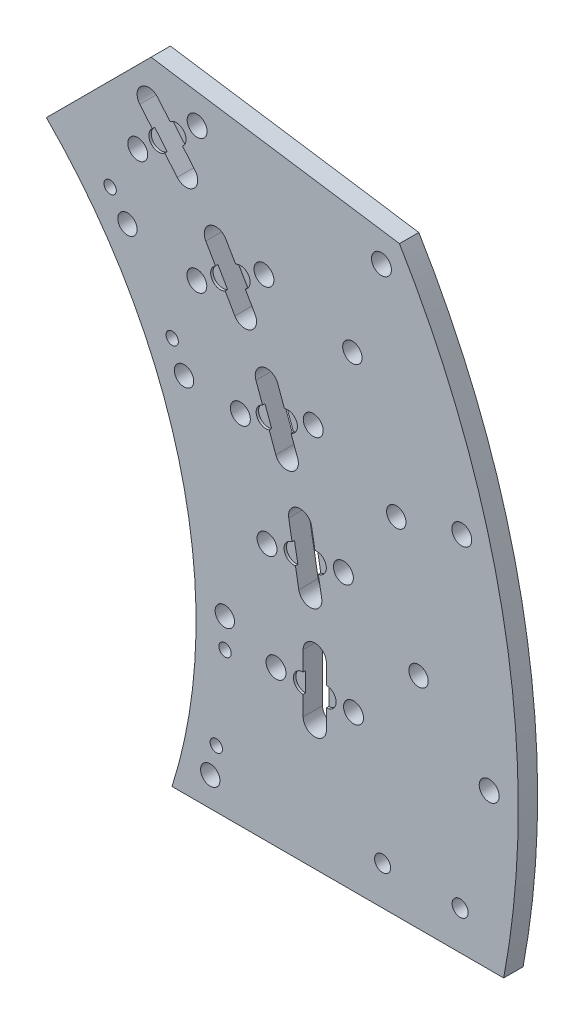
SolidWorks part; units mm, degrees
material "6061-T6 (SS)"
ref_plane "Front Plane" through (0, 0, 0) normal (0, 0, 1) x (1, 0, 0)
ref_plane "Top Plane" through (0, 0, 0) normal (0, 1, 0) x (1, 0, 0)
ref_plane "Right Plane" through (0, 0, 0) normal (1, 0, 0) x (0, 0, -1)
sketch "Sketch1" plane through (0, 0, 0) normal (0, 0, 1) x (1, 0, 0)
  line L0 (0, 0) -> (177.8, 0) construction
  line L1 (176.8984, 6.1774) -> (0, 0) construction
  line L2 (0, 0) -> (121.7947, 121.7947) construction
  line L3 (121.7947, 121.7947) -> (122.9173, 122.9173) construction
  line L4 (144.995, 101.5266) -> (0, 0) construction
  line L5 (0, 0) -> (163.5325, 67.7374) construction
  line L6 (167.4812, 0) -> (167.4812, -50.8) construction
  line L8 (159.5911, -50.8) -> (167.4812, -50.8) construction
  line L9 (172.1267, -41.275) -> (0, 0) construction
  line L10 (159.5911, -50.8) -> (268.2828, -50.8)
  line L11 (118.4271, 118.4271) -> (152.7152, 152.7152)
  line L12 (177.8, 0) -> (193.675, 0) construction
  line L13 (202.565, 0) -> (210.185, 0) construction
  line L14 (210.185, 0) -> (219.075, 0) construction
  line L15 (193.675, 0) -> (202.565, 0) construction
  line L16 (202.565, 0) -> (202.565, 9.525)
  line L17 (202.565, 0) -> (202.565, -9.525)
  line L18 (210.185, 9.525) -> (210.185, 0)
  line L19 (210.185, 0) -> (210.185, -9.525)
  line L20 (202.565, -9.525) -> (210.185, -9.525) construction
  line L21 (202.565, 9.525) -> (210.185, 9.525) construction
  line L22 (210.185, 9.525) -> (219.075, 0) construction
  line L23 (202.565, 9.525) -> (193.675, 0) construction
  line L24 (199.4876, 35.175) -> (201.1416, 25.7947)
  line L25 (199.4876, 35.175) -> (197.8336, 44.5553)
  line L26 (205.3378, 45.8785) -> (206.9918, 36.4982)
  line L27 (206.9918, 36.4982) -> (208.6458, 27.1179)
  line L28 (190.3488, 69.2813) -> (193.6066, 60.3307)
  line L29 (190.3488, 69.2813) -> (187.0911, 78.2319)
  line L30 (194.2516, 80.8381) -> (197.5093, 71.8875)
  line L31 (197.5093, 71.8875) -> (200.767, 62.9369)
  line L32 (175.4264, 101.2825) -> (180.1889, 93.0336)
  line L33 (175.4264, 101.2825) -> (170.6639, 109.5314)
  line L34 (177.263, 113.3414) -> (182.0255, 105.0925)
  line L35 (182.0255, 105.0925) -> (186.788, 96.8436)
  line L36 (155.1738, 130.2063) -> (161.2963, 122.9097)
  line L37 (155.1738, 130.2063) -> (149.0512, 137.5028)
  line L38 (154.8885, 142.4009) -> (161.0111, 135.1043)
  line L39 (161.0111, 135.1043) -> (167.1336, 127.8077)
  line L40 (0, 0) -> (193.675, 0) construction
  line L41 (0, 0) -> (190.7326, 33.6313) construction
  line L42 (0, 0) -> (254, 0) construction
  line L43 (254, 0) -> (263.525, 0) construction
  line L44 (254.5456, 68.2053) -> (0, 0) construction
  line L45 (152.7152, 152.7152) -> (234.123, 140.5088)
  line L46 (167.8212, 140.8187) -> (228.2193, 131.7625) construction
  line L47 (254.5456, 68.2053) -> (263.746, 70.6705) construction
  line L48 (0, 0) -> (240.3818, 21.0307) construction
  line L49 (0, 0) -> (240.3818, 21.0307) construction
  line L50 (0, 0) -> (233.0779, 62.453) construction
  line L51 (215.9, -50.8) -> (215.9, -25.4) construction
  line L52 (215.9, -25.4) -> (266.7, -25.4) construction
  line L53 (266.7, -25.4) -> (266.7, -50.8) construction
  line L54 (228.6, -38.1) -> (254, -38.1) construction
  line L55 (0, 0) -> (159.6519, 76.4361) construction
  line L56 (0, 0) -> (139.3238, 109.1792) construction
  arc A0 (172.2437, 0) -> (121.7947, 121.7947) centre (0, 0) ccw construction
  arc A1 (173.8312, 0) -> (122.9173, 122.9173) centre (0, 0) ccw construction
  circle A2 centre (176.8984, 6.1774) radius 3.175
  circle A3 centre (144.995, 101.5266) radius 3.175
  circle A4 centre (163.5325, 67.7374) radius 3.175
  arc A5 (167.4812, 0) -> (118.4271, 118.4271) centre (0, 0) ccw
  arc A6 (167.4812, 0) -> (159.5911, -50.8) centre (0, 0) cw
  arc A7 (173.8312, 0) -> (166.2428, -50.8) centre (0, 0) cw construction
  circle A8 centre (172.1267, -41.275) radius 3.175
  circle A9 centre (193.675, 0) radius 9.525 construction
  circle A10 centre (219.075, 0) radius 9.525 construction
  arc A11 (202.565, -9.525) -> (210.185, -9.525) centre (206.375, -9.525) ccw
  arc A12 (202.565, 9.525) -> (210.185, 9.525) centre (206.375, 9.525) cw
  circle A13 centre (193.675, 0) radius 3.2639
  circle A14 centre (219.075, 0) radius 3.2639
  circle A15 centre (215.7468, 38.042) radius 3.2639
  arc A16 (201.1416, 25.7947) -> (208.6458, 27.1179) centre (204.8937, 26.4563) ccw
  arc A17 (197.8336, 44.5553) -> (205.3378, 45.8785) centre (201.5857, 45.2169) cw
  circle A18 centre (190.7326, 33.6313) radius 3.2639
  circle A19 centre (205.8632, 74.9281) radius 3.2639
  arc A20 (193.6066, 60.3307) -> (200.767, 62.9369) centre (197.1868, 61.6338) ccw
  arc A21 (187.0911, 78.2319) -> (194.2516, 80.8381) centre (190.6713, 79.535) cw
  circle A22 centre (181.995, 66.2408) radius 3.2639
  circle A23 centre (189.7245, 109.5375) radius 3.2639
  arc A24 (180.1889, 93.0336) -> (186.788, 96.8436) centre (183.4885, 94.9386) ccw
  arc A25 (170.6639, 109.5314) -> (177.263, 113.3414) centre (173.9635, 111.4364) cw
  circle A26 centre (167.7275, 96.8375) radius 3.2639
  circle A27 centre (167.8212, 140.8187) radius 3.2639
  arc A28 (161.2963, 122.9097) -> (167.1336, 127.8077) centre (164.215, 125.3587) ccw
  arc A29 (149.0512, 137.5028) -> (154.8885, 142.4009) centre (151.9699, 139.9519) cw
  circle A30 centre (148.3637, 124.4919) radius 3.2639
  circle A31 centre (263.525, 0) radius 3.2639
  circle A32 centre (254.5456, 68.2053) radius 3.2639
  circle A33 centre (228.2193, 131.7625) radius 3.2639
  arc A34 (234.123, 140.5088) -> (268.2828, -50.8) centre (0, 0) cw
  circle A36 centre (240.3818, 21.0307) radius 3.175
  circle A37 centre (233.0779, 62.453) radius 3.175
  circle A38 centre (218.6921, 101.9778) radius 3.175
  arc A39 (210.185, 0) -> (203.9537, -50.8) centre (0, 0) cw construction
  circle A40 centre (228.6, -38.1) radius 2.6289
  circle A41 centre (254, -38.1) radius 2.6289
  circle A42 centre (159.6519, 76.4361) radius 9.525 construction
  circle A43 centre (159.6519, 76.4361) radius 2.0193
  circle A44 centre (159.6519, 76.4361) radius 3.175 construction
  circle A45 centre (139.3238, 109.1792) radius 2.0193
  circle A46 centre (139.3238, 109.1792) radius 9.525 construction
  circle A47 centre (176.9746, -3.3473) radius 2.0193
  circle A48 centre (176.9746, -3.3473) radius 9.525 construction
  circle A49 centre (174.0977, -31.9562) radius 2.0193
  circle A50 centre (174.0977, -31.9562) radius 9.525 construction
  point P3 (172.2437, 0)
  point P96 (0, 0)
  point P114 (266.7, -38.1)
  point P121 (177.8, -4.2997)
  point P124 (173.8312, -31.5473)
  point P132 (0, 0)
  dimension "D3" = 1.5875
  dimension "D4" = 6.35
  dimension "D5" = 2
  dimension "D7" = 10
  dimension "D8" = 6.35
  dimension "D9" = 6.35
  dimension "D11" = 6.35
  dimension "D13" = 6.35
  dimension "D15" = 19.05
  dimension "D16" = 7.62
  dimension "D17" = 19.05
  dimension "D21" = 15.875
  dimension "D22" = 6.5278
  dimension "D23" = 6.5278
  dimension "D28" = 6.5278
  dimension "D32" = 9.525
  dimension "D33" = 5
  dimension "D34" = 241.3
  dimension "D35" = 6.35
  dimension "D38" = 25.4
  dimension "D40" = 5.2578
  dimension "D41" = 5.2578
  dimension "D43" = 12.7
  dimension "D45" = 263.525
  dimension "D46" = 19.05
  dimension "D47" = 4.0386
  dimension "D48" = 6.35
  dimension "D51" = 4.0386
  dimension "D52" = 19.05
  dimension "D1" = 177.8
  dimension "D2" = 5.5562
  dimension "D6" = 45
  dimension "D10" = 22.5
  dimension "D12" = 50.8
  dimension "D14" = 9.525
  dimension "D18" = 9.525
  dimension "D19" = 9.525
  dimension "D20" = 25.4
  dimension "D25" = 10
  dimension "D26" = 254
  dimension "D27" = 9.525
  dimension "D30" = 15
  dimension "D31" = 9.525
  dimension "D37" = 10
  dimension "D39" = 50.8
  dimension "D42" = 25.4
  dimension "D44" = 215.9
  dimension "D50" = 12.5
  dimension "D54" = 12.7
  dimension "D24" = 5
  dimension "D29" = 3
  dimension "D36" = 3
  dimension "D49" = 2
  dimension "D53" = 2
extrude "Boss-Extrude1" add sketch "Sketch1" along normal blind 6.35 contours A34 L45 L11 A5 A6 L10 A33 A32 A31 A30 A27 A26 A23 A22 A19 A18 A15 A14 A13 A8 A4 A3 A2 L16 A12 L18 L19 A11 L17 L25 A17 L26 region at (208.0177, 48.2155, 0)
sketch "Sketch2" plane through (0, 0, 6.35) normal (0, 0, 1) x (1, 0, 0)
  line L0 (202.565, -9.525) -> (202.565, 9.525) construction
  line L1 (210.185, 9.525) -> (210.185, -9.525) construction
  line L2 (0, 0) -> (202.565, 0) construction
  line L3 (0, 0) -> (199.4876, 35.175) construction
  circle A0 centre (202.565, 0) radius 3.175
  circle A1 centre (210.185, 0) radius 3.175
  circle A2 centre (199.4876, 35.175) radius 3.175
  circle A3 centre (206.9918, 36.4982) radius 3.175
  circle A4 centre (190.3488, 69.2813) radius 3.175
  circle A5 centre (197.5093, 71.8875) radius 3.175
  circle A6 centre (175.4264, 101.2825) radius 3.175
  circle A7 centre (182.0255, 105.0925) radius 3.175
  circle A8 centre (155.1738, 130.2063) radius 3.175
  circle A9 centre (161.0111, 135.1043) radius 3.175
  dimension "D1" = 6.35
  dimension "D2" = 6.35
  dimension "D4" = 10
  dimension "D3" = 5
extrude "Cut-Extrude1" cut sketch "Sketch2" against normal blind 0.7937
sketch "Sketch3" plane through (0, 0, 6.35) normal (0, 0, 1) x (1, 0, 0)
  line L0 (0, 0) -> (167.4812, 0) construction
  line L1 (159.5911, -50.8) -> (159.5911, 0) construction
  arc A0 (159.5911, -50.8) -> (118.4271, 118.4271) centre (0, 0) ccw construction
  dimension "D1" = 7.8901
